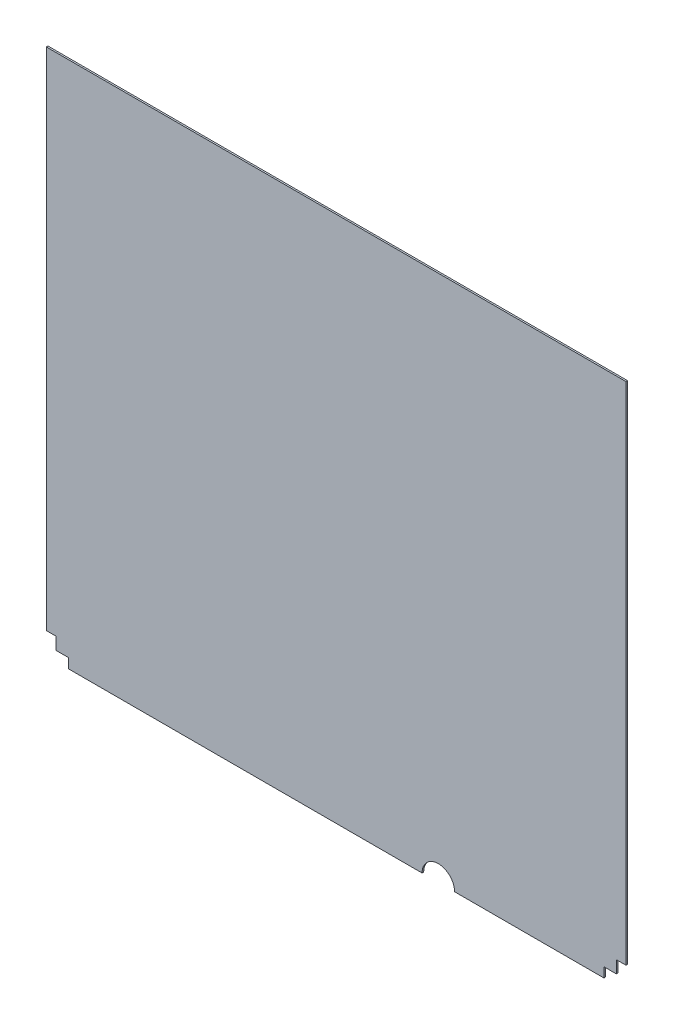
SolidWorks part; units mm, degrees
ref_plane "Front Plane" through (0, 0, 0) normal (0, 0, 1) x (1, 0, 0)
ref_plane "Top Plane" through (0, 0, 0) normal (0, 1, 0) x (1, 0, 0)
ref_plane "Right Plane" through (0, 0, 0) normal (1, 0, 0) x (0, 0, -1)
sketch "Sketch1" plane through (0, 0, 0) normal (0, 0, 1) x (1, 0, 0)
  line L0 (0, 34.544) -> (15.24, 34.544)
  line L1 (0, 0) -> (907.001, 0)
  line L2 (0, 0) -> (0, 825.5)
  line L3 (0, 825.5) -> (907.001, 825.5)
  line L4 (907.001, 0) -> (907.001, 825.5)
  line L5 (0, 0) -> (914.4, 0) construction
  line L6 (0, 0) -> (0, 914.4) construction
  line L7 (0, 914.4) -> (914.4, 914.4) construction
  line L8 (914.4, 0) -> (914.4, 914.4) construction
  line L9 (15.24, 34.544) -> (15.24, 15.24)
  line L10 (15.24, 15.24) -> (34.544, 15.24)
  line L11 (34.544, 15.24) -> (34.544, 0)
  line L12 (907.001, 34.544) -> (891.761, 34.544)
  line L13 (891.761, 34.544) -> (891.761, 15.24)
  line L14 (891.761, 15.24) -> (872.457, 15.24)
  line L15 (872.457, 15.24) -> (872.457, 0)
  arc A0 (638.7043, 0) -> (587.9043, 0) centre (613.3043, 0) ccw
  dimension "D13" = 25.4
  dimension "D1" = 825.5
  dimension "D2" = 907.001
  dimension "D3" = 914.4
  dimension "D4" = 914.4
  dimension "D5" = 15.24
  dimension "D6" = 15.24
  dimension "D7" = 34.544
  dimension "D8" = 34.544
  dimension "D9" = 15.24
  dimension "D10" = 15.24
  dimension "D11" = 34.544
  dimension "D12" = 34.544
extrude "Boss-Extrude1" add sketch "Sketch1" along normal blind 2.54 contours L15 L14 L13 L12 L4 L3 L2 L0 L9 L10 L11 L1 region at (453.2834, 414.1736, 0)
